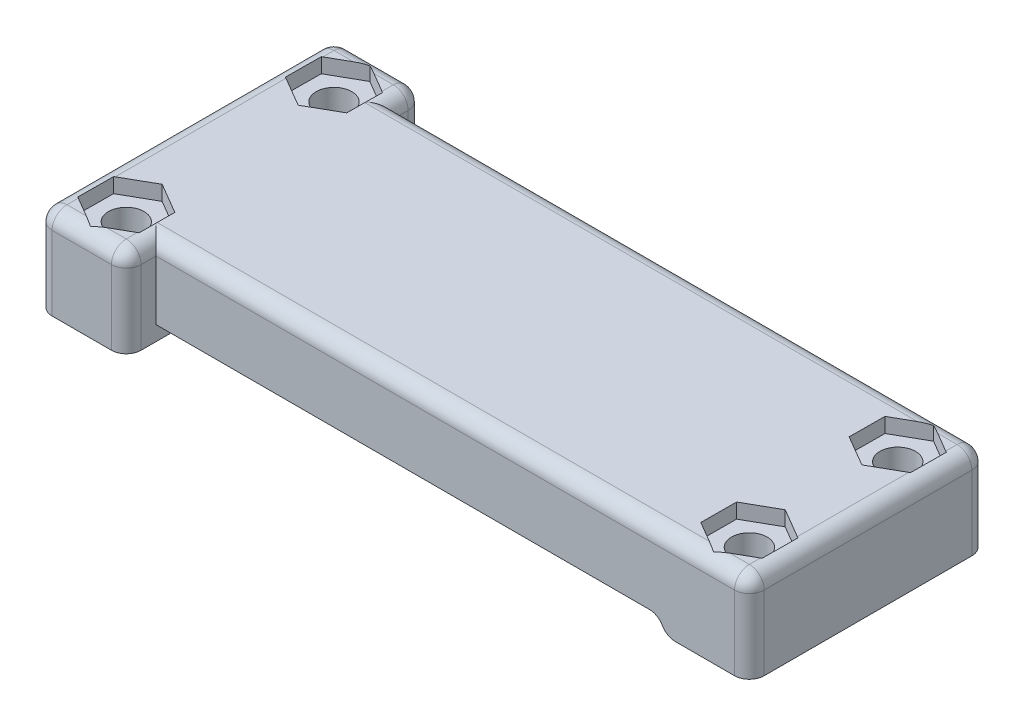
SolidWorks part; units mm, degrees
material "ABS PC"
ref_plane "前基準面" through (0, 0, 0) normal (0, 0, 1) x (1, 0, 0)
ref_plane "上基準面" through (0, 0, 0) normal (0, 1, 0) x (1, 0, 0)
ref_plane "右基準面" through (0, 0, 0) normal (1, 0, 0) x (0, 0, -1)
sketch "草圖1" plane through (0, 0, 0) normal (0, 1, 0) x (1, 0, 0)
  line L0 (0, 0) -> (-20, 0) construction
  line L1 (-20, -8) -> (20, -8)
  line L2 (-20, -4) -> (-20, 4)
  line L3 (-20, 8) -> (20, 8)
  line L4 (20, -8) -> (20, 8)
  line L5 (-20, 4) -> (-26, 4)
  line L6 (-26, 4) -> (-26, 10)
  line L7 (-26, 10) -> (-20, 10)
  line L8 (-20, 10) -> (-20, 8)
  line L9 (-20, -10) -> (-20, -8)
  line L10 (-26, -10) -> (-20, -10)
  line L11 (-26, -4) -> (-26, -10)
  line L12 (-20, -4) -> (-26, -4)
  dimension "D1" = 16
  dimension "D3" = 20
  dimension "D4" = 40
extrude "填料-伸長1" add sketch "草圖1" along normal blind 6
sketch "草圖2" plane through (0, 0, 0) normal (0, 1, 0) x (1, 0, 0)
  line L1 (-26, 4) -> (-20, 4)
  line L2 (-26, 4) -> (-26, -4)
  line L3 (-26, -4) -> (-20, -4)
  line L4 (-20, 4) -> (-20, -4)
extrude "填料-伸長2" add sketch "草圖2" along normal blind 6
sketch "草圖4" plane through (0, 0, 0) normal (0, 1, 0) x (1, 0, 0)
  line L0 (-20, 0) -> (0, 0) construction
  line L1 (-26, 10) -> (-23, 10) construction
  line L2 (-26, -10) -> (-23, -10) construction
  line L3 (-26, 10) -> (-20, 10) construction
  line L4 (-23, 10) -> (-23, 7) construction
  line L5 (-23, -10) -> (-23, -7) construction
  line L6 (-25.0866, -8.1859) -> (-23.0163, -9.4)
  line L7 (-20.9297, -8.2141) -> (-20.9134, -5.8141)
  line L8 (-23.0163, -9.4) -> (-20.9297, -8.2141)
  line L9 (-22.9837, -4.6) -> (-25.0703, -5.7859)
  line L10 (-22.9837, 9.4) -> (-25.0703, 8.2141)
  line L11 (-25.0703, 8.2141) -> (-25.0866, 5.8141)
  line L12 (-25.0866, 5.8141) -> (-23.0163, 4.6)
  line L13 (-23.0163, 4.6) -> (-20.9297, 5.7859)
  line L14 (-20.9297, 5.7859) -> (-20.9134, 8.1859)
  line L15 (-20.9134, 8.1859) -> (-22.9837, 9.4)
  line L16 (-25.0703, -5.7859) -> (-25.0866, -8.1859)
  line L17 (-20.9134, -5.8141) -> (-22.9837, -4.6)
  line L19 (19.0866, 6.1859) -> (17.0163, 7.4)
  line L20 (14.9297, 6.2141) -> (14.9134, 3.8141)
  line L21 (14.9134, 3.8141) -> (16.9837, 2.6)
  line L22 (16.9837, 2.6) -> (19.0703, 3.7859)
  line L23 (17.0163, 7.4) -> (14.9297, 6.2141)
  line L24 (19.0703, 3.7859) -> (19.0866, 6.1859)
  line L25 (19.0866, -3.8141) -> (17.0163, -2.6)
  line L26 (14.9297, -3.7859) -> (14.9134, -6.1859)
  line L27 (14.9134, -6.1859) -> (16.9837, -7.4)
  line L28 (16.9837, -7.4) -> (19.0703, -6.2141)
  line L29 (17.0163, -2.6) -> (14.9297, -3.7859)
  line L30 (19.0703, -6.2141) -> (19.0866, -3.8141)
  circle A0 centre (-23, -7) radius 2.0785 construction
  circle A1 centre (-23, 7) radius 2.0785 construction
  circle A2 centre (17, 5) radius 2.0785 construction
  circle A3 centre (17, -5) radius 2.0785 construction
  point P19 (-25.1955, 7)
  point P21 (-25.3, -7)
  point P27 (14.8045, 5)
  point P33 (14.8045, -5)
  dimension "D1" = 4.8
  dimension "D2" = 4.8
  dimension "D3" = 4.8
  dimension "D4" = 4.8
extrude "除料-伸長2" cut sketch "草圖4" along normal blind 1 from offset 5
fillet "圓角8" radius 1 2 edges at (0, 6, -8) (0, 6, 8)
fillet "圓角9" radius 1 5 edges at (20, 2.5, 8) (20, 5.7071, 7.7071) (20, 2.5, -8) (20, 5.7071, -7.7071) (20, 6, 0)
fillet "圓角10" radius 1 1 edges at (-20, 6, -8.5)
fillet "圓角11" radius 1 1 edges at (-20, 6, 8.5)
fillet "圓角12" radius 1 6 edges at (-23.5, 6, -10) (-20.2929, 5.7071, -10) (-23.5, 6, 10) (-20.2929, 5.7071, 10) (-20, 2.5, -10) (-20, 2.5, 10)
fillet "圓角13" radius 1 5 edges at (-26, 5.7071, 9.7071) (-26, 6, 0) (-26, 5.7071, -9.7071) (-26, 2.5, 10) (-26, 2.5, -10)
sketch "草圖6" plane through (0, 0, 0) normal (0, 1, 0) x (1, 0, 0)
  line L0 (-20, 8) -> (20, 8) construction
  line L1 (-20, -10) -> (-26, -10) construction
  line L2 (-20, -10) -> (-20, 10) construction
  line L3 (-20, 10) -> (-26, 10) construction
  line L4 (-26, -10) -> (-26, 10) construction
  line L5 (20, -8) -> (14, -8) construction
  line L6 (20, -8) -> (20, 8) construction
  line L7 (20, 8) -> (14, 8) construction
  line L8 (14, -8) -> (14, 8) construction
  dimension "D1" = 6
sketch "草圖8" plane through (0, 0, 0) normal (0, 1, 0) x (1, 0, 0)
  line L0 (-20, 4) -> (-20, 8)
  line L1 (-20, -8) -> (14, -8)
  line L2 (-20, -8) -> (-20, -4)
  line L3 (-20, 8) -> (14, 8)
  line L4 (14, -8) -> (14, 8)
  line L5 (-20, -4) -> (-26, -4)
  line L7 (-20, 4) -> (-26, 4)
  line L8 (-26, -4) -> (-26, 4)
extrude "除料-伸長5" cut sketch "草圖8" along normal blind 1
fillet "圓角14" radius 1 1 edges at (14, 0, 0)
fillet "圓角15" radius 1 1 edges at (14, 1, 0)
sketch "草圖9" plane through (0, 0, 0) normal (0, 1, 0) x (1, 0, 0)
  line L0 (-22.9837, 9.4) -> (-23.0163, 4.6) construction
  line L1 (-22.9837, -4.6) -> (-23.0163, -9.4) construction
  line L2 (-25.0703, 8.2141) -> (-25.0866, 5.8141) construction
  line L3 (-25.0785, 7.0141) -> (-23, 7) construction
  line L4 (-25.0785, -6.9859) -> (-23, -7) construction
  line L5 (17.0163, 7.4) -> (16.9837, 2.6) construction
  line L6 (14.9215, 5.0141) -> (17, 5) construction
  line L7 (17.0163, -2.6) -> (16.9837, -7.4) construction
  line L8 (14.9215, -4.9859) -> (17, -5) construction
  circle A0 centre (-23, 7) radius 1.2
  circle A1 centre (-23, -7) radius 1.2
  circle A2 centre (17, 5) radius 1.2
  circle A3 centre (17, -5) radius 1.2
extrude "除料-伸長6" cut sketch "草圖9" along normal blind 5
